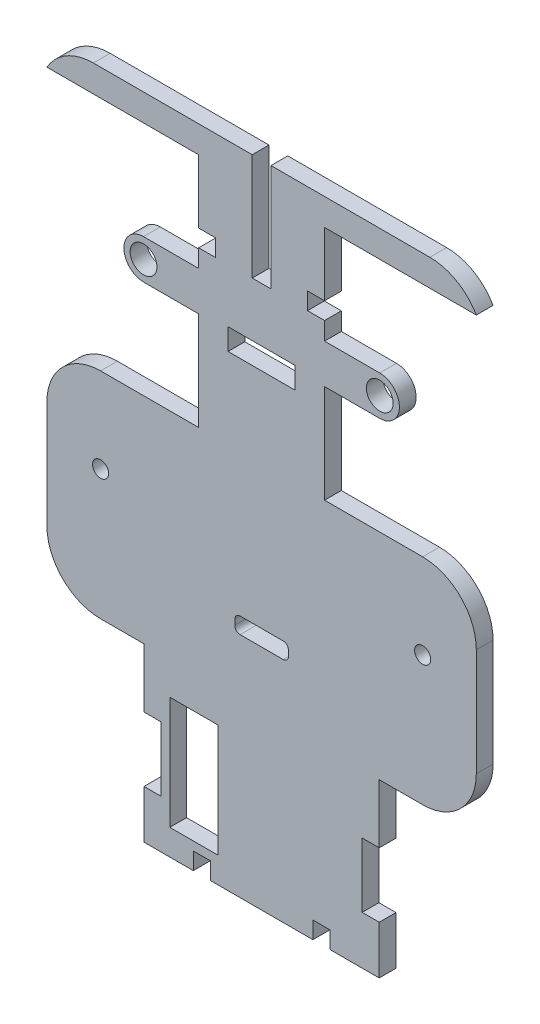
SolidWorks part; units mm, degrees
ref_plane "Front Plane" through (0, 0, 0) normal (0, 0, 1) x (1, 0, 0)
ref_plane "Top Plane" through (0, 0, 0) normal (0, 1, 0) x (1, 0, 0)
ref_plane "Right Plane" through (0, 0, 0) normal (1, 0, 0) x (0, 0, -1)
sketch "Sketch3" plane through (0, 0, 0) normal (0, 0, 1) x (1, 0, 0)
  line L0 (0, 23.3143) -> (0, 40.6)
  line L1 (0, 60.5) -> (40, 60.5) construction
  line L2 (0, 60.5) -> (0, -60.5) construction
  line L3 (0, -60.5) -> (40, -60.5) construction
  line L4 (40, 60.5) -> (40, -60.5) construction
  line L5 (0, 40.6) -> (1.75, 40.6)
  line L6 (1.75, 40.6) -> (1.75, 60.5)
  line L7 (1.75, 60.5) -> (40, 60.5)
  line L8 (40, 60.5) -> (40, 55.5)
  line L9 (40, 55.5) -> (11.73, 55.5)
  line L10 (11.73, 55.5) -> (11.73, 43.67)
  line L11 (11.73, 43.67) -> (8.55, 43.67)
  line L12 (8.55, 43.67) -> (8.55, 40.49)
  line L13 (8.55, 40.49) -> (11.73, 40.49)
  line L14 (11.73, 40.49) -> (11.73, 37.16)
  line L15 (11.73, 37.16) -> (22, 37.16)
  line L16 (22, 37.16) -> (22, 29.83) construction
  line L17 (22, 29.83) -> (11.73, 29.83)
  line L18 (11.73, 29.83) -> (11.73, 11.5)
  line L19 (11.73, 11.5) -> (40, 11.5)
  line L20 (40, 11.5) -> (40, -28.5)
  line L21 (40, -28.5) -> (21.91, -28.5)
  line L22 (21.91, -28.5) -> (21.91, -39.5)
  line L23 (21.91, -39.5) -> (18.73, -39.5)
  line L24 (18.73, -39.5) -> (18.73, -51.5)
  line L25 (18.73, -51.5) -> (21.91, -51.5)
  line L26 (21.91, -51.5) -> (21.91, -60.5)
  line L27 (21.91, -60.5) -> (12.73, -60.5)
  line L28 (12.73, -60.5) -> (12.73, -57.32)
  line L29 (12.73, -57.32) -> (9.55, -57.32)
  line L30 (9.55, -57.32) -> (9.55, -60.5)
  line L31 (9.55, -60.5) -> (0, -60.5)
  line L32 (0, 23.3143) -> (0, -60.5)
  arc A0 (22, 29.83) -> (22, 37.16) centre (22, 33.495) ccw
  circle A1 centre (22, 33.495) radius 2.5
  circle A2 centre (30, -4.33) radius 1.5
  point P0 (11.73, 2.897)
  point P5 (0, 0)
  dimension "D22" = 5
  dimension "D23" = 3
  dimension "D1" = 40
  dimension "D2" = 121
  dimension "D3" = 1.75
  dimension "D4" = 19.9
  dimension "D5" = 5
  dimension "D6" = 28.27
  dimension "D7" = 11.83
  dimension "D8" = 3.18
  dimension "D9" = 3.18
  dimension "D10" = 3.33
  dimension "D11" = 10.27
  dimension "D12" = 7.33
  dimension "D13" = 18.33
  dimension "D14" = 40
  dimension "D15" = 18.09
  dimension "D16" = 11
  dimension "D17" = 3.18
  dimension "D18" = 12
  dimension "D19" = 3.18
  dimension "D20" = 3.18
  dimension "D21" = 9.18
  dimension "D24" = 15.83
  dimension "D25" = 10
extrude "Boss-Extrude1" add sketch "Sketch3" along normal blind 3.125
mirror "Mirror1" about plane through (0, 23.3143, 3.125) normal (1, 0, 0) of "Boss-Extrude1"
fillet "Fillet1" radius 10 6 edges at (-40, 60.5, 1.5625) (-40, 11.5, 1.5625) (-40, -28.5, 1.5625) (40, -28.5, 1.5625) (40, 11.5, 1.5625) (40, 60.5, 1.5625)
sketch "Sketch4" plane through (0, 0, 3.125) normal (0, 0, 1) x (1, 0, 0)
  line L0 (11.73, 11.5) -> (11.73, 29.83) construction
  line L1 (-6.25, 30.5) -> (6.25, 30.5)
  line L2 (-6.25, 30.5) -> (-6.25, 26.5)
  line L3 (-6.25, 26.5) -> (6.25, 26.5)
  line L4 (6.25, 30.5) -> (6.25, 26.5)
  line L5 (-6.25, 30.5) -> (6.25, 26.5) construction
  line L6 (-6.25, 26.5) -> (6.25, 30.5) construction
  line L7 (-30, 11.5) -> (-11.73, 11.5) construction
  line L8 (-9.55, -60.5) -> (9.55, -60.5) construction
  line L9 (-8.11, -55.7) -> (-17.11, -55.7)
  line L10 (-8.11, -55.7) -> (-8.11, -34.7)
  line L11 (-8.11, -34.7) -> (-17.11, -34.7)
  line L12 (-17.11, -55.7) -> (-17.11, -34.7)
  line L13 (-8.11, -55.7) -> (-17.11, -34.7) construction
  line L14 (-8.11, -34.7) -> (-17.11, -55.7) construction
  line L15 (-21.91, -60.5) -> (-21.91, -51.5) construction
  line L16 (21.91, -28.5) -> (30, -28.5) construction
  line L17 (-4, -15.06) -> (4, -15.06)
  line L18 (-5, -16.06) -> (-5, -17.06)
  line L19 (-4, -18.06) -> (4, -18.06)
  line L20 (5, -16.06) -> (5, -17.06)
  line L21 (-5, -15.06) -> (5, -18.06) construction
  line L22 (-5, -18.06) -> (5, -15.06) construction
  line L23 (-40, -18.5) -> (-40, 1.5) construction
  arc A0 (5, -16.06) -> (4, -15.06) centre (4, -16.06) ccw
  arc A1 (4, -18.06) -> (5, -17.06) centre (4, -17.06) ccw
  arc A2 (-5, -17.06) -> (-4, -18.06) centre (-4, -17.06) ccw
  arc A3 (-5, -16.06) -> (-4, -15.06) centre (-4, -16.06) cw
  point P0 (0, 28.5)
  point P9 (-12.61, -45.2)
  point P18 (0, -16.56)
  point P27 (0, 0)
  dimension "D13" = 1
  dimension "D1" = 4
  dimension "D2" = 12.5
  dimension "D3" = 5.48
  dimension "D4" = 15
  dimension "D5" = 21
  dimension "D6" = 9
  dimension "D7" = 4.8
  dimension "D8" = 4.8
  dimension "D9" = 10
  dimension "D10" = 3
  dimension "D11" = 10.44
  dimension "D12" = 35
extrude "Cut-Extrude2" cut sketch "Sketch4" against normal through all
